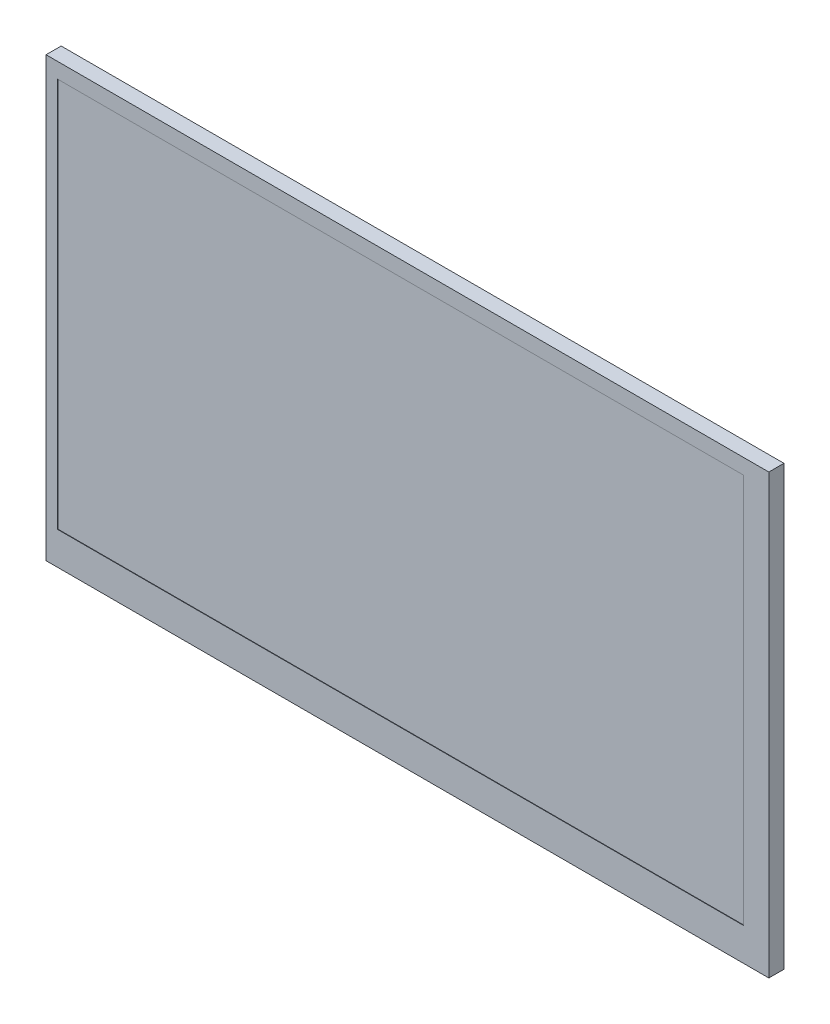
SolidWorks part; units mm, degrees
ref_plane "Plan de face" through (0, 0, 0) normal (0, 0, 1) x (1, 0, 0)
ref_plane "Plan de dessus" through (0, 0, 0) normal (0, 1, 0) x (1, 0, 0)
ref_plane "Plan de droite" through (0, 0, 0) normal (1, 0, 0) x (0, 0, -1)
sketch "Esquisse1" plane through (0, 0, 0) normal (0, 0, 1) x (1, 0, 0)
  line L0 (82.615, 53.25) -> (-82.615, -53.25) construction
  line L1 (0, 50.0368) -> (0, -50.0368) construction
  line L2 (-82.615, 53.25) -> (-82.615, -53.25)
  line L3 (-74.611, 50.0368) -> (74.611, 50.0368)
  line L4 (82.615, 53.25) -> (82.615, -53.25)
  line L5 (-78.613, 50.0368) -> (-78.613, 53.25) construction
  line L7 (-74.611, 50.0368) -> (-74.611, 53.25)
  line L8 (78.613, 50.0368) -> (78.613, 53.25) construction
  line L9 (74.611, 50.0368) -> (74.611, 53.25)
  line L11 (78.613, -50.0368) -> (78.613, -53.25) construction
  line L13 (74.611, -50.0368) -> (74.611, -53.25)
  line L14 (-78.613, -50.0368) -> (-78.613, -53.25) construction
  line L15 (-74.611, -50.0368) -> (-74.611, -53.25)
  line L17 (-74.611, -50.0368) -> (74.611, -50.0368)
  circle A0 centre (-78.613, 53.25) radius 1.524
  arc A1 (-74.611, 53.25) -> (-82.615, 53.25) centre (-78.613, 53.25) ccw
  circle A2 centre (-78.613, -53.25) radius 1.524
  arc A3 (82.615, 53.25) -> (74.611, 53.25) centre (78.613, 53.25) ccw
  circle A4 centre (78.613, -53.25) radius 1.524
  arc A5 (74.611, -53.25) -> (82.615, -53.25) centre (78.613, -53.25) ccw
  circle A6 centre (78.613, 53.25) radius 1.524
  arc A7 (-82.615, -53.25) -> (-74.611, -53.25) centre (-78.613, -53.25) ccw
  point P7 (-78.613, 53.25)
  point P12 (78.613, 51.625)
  point P21 (78.613, -51.625)
  point P28 (-78.613, -51.625)
  dimension "D5" = 3.048
  dimension "D1" = 100.0736
  dimension "D2" = 165.23
  dimension "D3" = 106.5
  dimension "D4" = 157.226
extrude "Boss.-Extru.1" add sketch "Esquisse1" along normal blind 2.1
sketch "Esquisse2" plane through (0, 0, 2.1) normal (0, 0, 1) x (1, 0, 0)
  line L0 (-74.5, 40) -> (74.5, -40) construction
  line L1 (-74.5, 40) -> (-49.1, 40)
  line L2 (-74.5, 40) -> (-74.5, 14.6)
  line L3 (-74.5, 14.6) -> (-49.1, 14.6)
  line L4 (-49.1, 40) -> (-49.1, 14.6)
  line L5 (-74.5, -14.6) -> (-49.1, -14.6)
  line L6 (-74.5, -14.6) -> (-74.5, -40)
  line L7 (-74.5, -40) -> (-49.1, -40)
  line L8 (-49.1, -14.6) -> (-49.1, -40)
  line L9 (49.1, 40) -> (74.5, 40)
  line L10 (49.1, 40) -> (49.1, 14.6)
  line L11 (49.1, 14.6) -> (74.5, 14.6)
  line L12 (74.5, 40) -> (74.5, 14.6)
  line L13 (49.1, -14.6) -> (74.5, -14.6)
  line L14 (49.1, -14.6) -> (49.1, -40)
  line L15 (49.1, -40) -> (74.5, -40)
  line L16 (74.5, -14.6) -> (74.5, -40)
  line L17 (-74.5, -40) -> (74.5, 40) construction
  dimension "D1" = 25.4
  dimension "D2" = 149
  dimension "D3" = 80
extrude "Boss.-Extru.2" add sketch "Esquisse2" along normal blind 2.3
sketch "Esquisse3" plane through (0, 0, 4.4) normal (0, 0, 1) x (1, 0, 0)
  line L1 (82.475, -50) -> (-82.475, -50)
  line L2 (82.475, -50) -> (82.475, 50)
  line L3 (82.475, 50) -> (-82.475, 50)
  line L4 (-82.475, -50) -> (-82.475, 50)
  line L5 (82.475, -50) -> (-82.475, 50) construction
  line L6 (82.475, 50) -> (-82.475, -50) construction
  point P0 (0, 0)
  dimension "D1" = 100
  dimension "D2" = 164.95
extrude "Boss.-Extru.3" add sketch "Esquisse3" along normal blind 3.45
sketch "Esquisse4" plane through (0, 0, 7.85) normal (0, 0, 1) x (1, 0, 0)
  line L0 (-82.475, 50) -> (-82.475, -50) construction
  line L1 (-79.855, 46.5) -> (76.645, 46.5)
  line L2 (-79.855, 46.5) -> (-79.855, -42.5)
  line L3 (-79.855, -42.5) -> (76.645, -42.5)
  line L4 (76.645, 46.5) -> (76.645, -42.5)
  line L5 (82.475, 50) -> (-82.475, 50) construction
  dimension "D1" = 156.5
  dimension "D2" = 2.62
  dimension "D3" = 3.5
  dimension "D4" = 89
extrude "Enlèv. mat.-Extru.1" cut sketch "Esquisse4" against normal blind 0.1
sketch "Esquisse5" plane through (0, 0, 0) normal (0, 0, -1) x (-1, 0, 0)
  line L0 (74.611, -50.0368) -> (-74.611, -50.0368) construction
  line L1 (23.415, 3.5632) -> (53.215, 3.5632)
  line L2 (23.415, 3.5632) -> (23.415, -3.8368)
  line L3 (23.415, -3.8368) -> (53.215, -3.8368)
  line L4 (53.215, 3.5632) -> (53.215, -3.8368)
  line L5 (82.615, 53.25) -> (82.615, -53.25) construction
  dimension "D1" = 29.8
  dimension "D2" = 7.4
  dimension "D3" = 46.2
  dimension "D4" = 29.4
extrude "Enlèv. mat.-Extru.2" cut sketch "Esquisse5" against normal blind 2.1
fillet "Congé1" radius 1 4 edges at (-23.415, 3.5632, 1.05) (-23.415, -3.8368, 1.05) (-53.215, -3.8368, 1.05) (-53.215, 3.5632, 1.05)
sketch "Esquisse6" plane through (0, 0, 0) normal (0, 0, -1) x (-1, 0, 0)
  line L0 (38.315, -3.8368) -> (38.315, 9.0632) construction
  line L1 (25.065, 9.0632) -> (51.565, 9.0632)
  line L2 (25.065, 9.0632) -> (25.065, 3.6632)
  line L3 (25.065, 3.6632) -> (51.565, 3.6632)
  line L4 (51.565, 9.0632) -> (51.565, 3.6632)
  line L5 (24.415, -3.8368) -> (52.215, -3.8368) construction
  line L7 (52.215, 3.5632) -> (24.415, 3.5632) construction
  dimension "D1" = 26.5
  dimension "D2" = 5.4
  dimension "D3" = 0.1
extrude "Boss.-Extru.4" add sketch "Esquisse6" along normal blind 2
sketch "Esquisse7" plane through (0, 0, 0) normal (0, 0, -1) x (-1, 0, 0)
  line L0 (-84.815, 1.0172) -> (-98.2984, 1.0172) construction
  line L1 (-84.815, 8.5172) -> (-73.225, 8.5172)
  line L2 (-84.815, 8.5172) -> (-84.815, -6.4828)
  line L3 (-84.815, -6.4828) -> (-73.225, -6.4828)
  line L4 (-73.225, 8.5172) -> (-73.225, -6.4828)
  line L5 (74.611, -50.0368) -> (-74.611, -50.0368) construction
  line L6 (-82.615, -53.25) -> (-82.615, 53.25) construction
  dimension "D1" = 51.054
  dimension "D2" = 15
  dimension "D3" = 11.59
  dimension "D4" = 2.2
extrude "Boss.-Extru.5" add sketch "Esquisse7" along normal blind 6.16
sketch "Esquisse8" plane through (0, 0, 0) normal (0, 0, -1) x (-1, 0, 0)
  line L0 (-83.415, -20.3188) -> (-92.7236, -20.3188) construction
  line L1 (-83.415, -16.3788) -> (-77.915, -16.3788)
  line L2 (-83.415, -16.3788) -> (-83.415, -24.2588)
  line L3 (-83.415, -24.2588) -> (-77.915, -24.2588)
  line L4 (-77.915, -16.3788) -> (-77.915, -24.2588)
  line L5 (74.611, -50.0368) -> (-74.611, -50.0368) construction
  line L6 (-82.615, -53.25) -> (-82.615, -6.4828) construction
  dimension "D2" = 7.88
  dimension "D3" = 5.5
  dimension "D4" = 0.8
extrude "Boss.-Extru.6" add sketch "Esquisse8" along normal blind 2.8
sketch "Esquisse9" plane through (0, 0, 0) normal (0, 0, -1) x (-1, 0, 0)
  line L0 (-74.611, 50.0368) -> (74.611, 50.0368) construction
  line L1 (-59.615, 7.5368) -> (-45.775, 7.5368)
  line L2 (-59.615, 7.5368) -> (-59.615, -6.3032)
  line L3 (-59.615, -6.3032) -> (-45.775, -6.3032)
  line L4 (-45.775, 7.5368) -> (-45.775, -6.3032)
  line L5 (-82.615, 8.5172) -> (-82.615, 53.25) construction
  dimension "D1" = 13.84
  dimension "D2" = 42.5
  dimension "D3" = 23
extrude "Boss.-Extru.7" add sketch "Esquisse9" along normal blind 1
sketch "Esquisse10" plane through (0, 0, 2.1) normal (0, 0, 1) x (1, 0, 0)
  circle A0 centre (-78.613, 53.25) radius 1.524
  circle A1 centre (-78.613, 53.25) radius 3.175
  circle A2 centre (-78.613, -53.25) radius 1.524
  circle A3 centre (-78.613, -53.25) radius 3.175
  circle A4 centre (78.613, -53.25) radius 1.524
  circle A5 centre (78.613, -53.25) radius 3.175
  circle A6 centre (78.613, 53.25) radius 1.524
  circle A7 centre (78.613, 53.25) radius 3.175
  circle A8 centre (78.613, 53.25) radius 1.524 construction
  circle A9 centre (-78.613, 53.25) radius 1.524 construction
  circle A10 centre (-78.613, -53.25) radius 1.524 construction
  circle A11 centre (78.613, -53.25) radius 1.524 construction
  dimension "D1" = 6.35
extrude "Boss.-Extru.8" add sketch "Esquisse10" along normal blind 0.1 and the other way blind 2.11
split "Split1" bodies to split 110 resulting bodies 111 split by face at (0, 0, 4.4)
